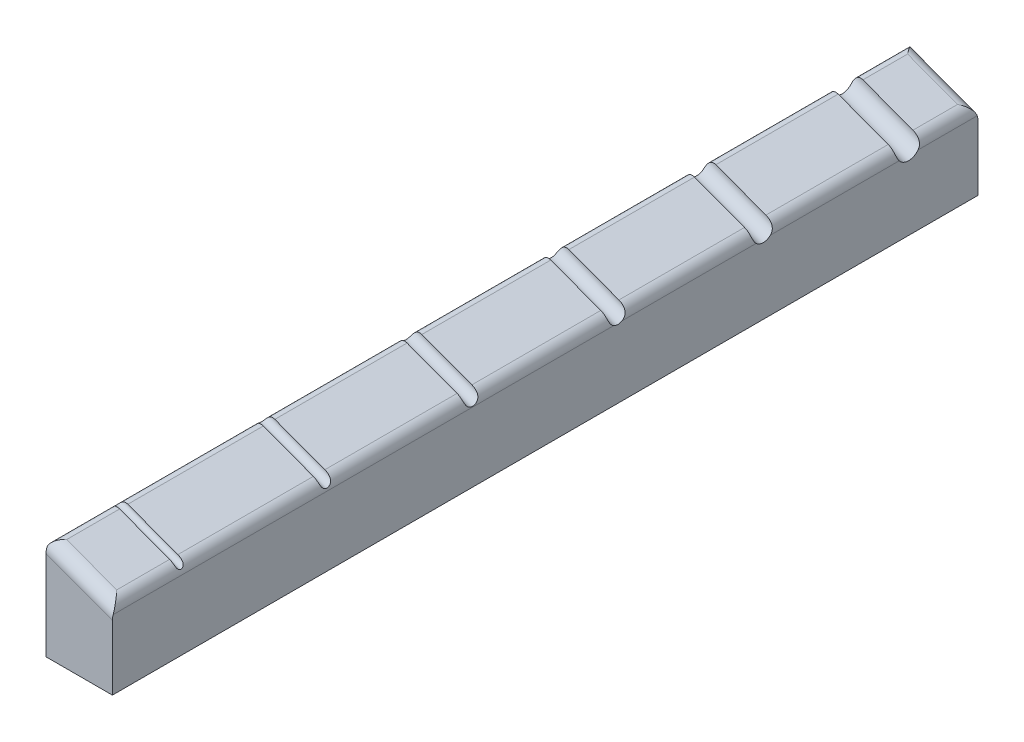
SolidWorks part; units mm, degrees
ref_plane "Front Plane" through (0, 0, 0) normal (0, 0, 1) x (1, 0, 0)
ref_plane "Top Plane" through (0, 0, 0) normal (0, 1, 0) x (1, 0, 0)
ref_plane "Right Plane" through (0, 0, 0) normal (1, 0, 0) x (0, 0, -1)
sketch "Sketch1" plane through (0, 0, 0) normal (0, 1, 0) x (1, 0, 0)
  line L1 (0, 0) -> (3.22, 0)
  line L2 (0, 0) -> (0, -41.98)
  line L3 (0, -41.98) -> (3.22, -41.98)
  line L4 (3.22, 0) -> (3.22, -41.98)
  dimension "D1" = 41.98
  dimension "D2" = 3.22
extrude "Boss-Extrude1" add sketch "Sketch1" along normal blind 4.98
sketch "Sketch2" plane through (0, 0, 41.98) normal (0, 0, 1) x (1, 0, 0)
  line L0 (0, 4.98) -> (3.22, 4.98)
  line L1 (3.22, 4.98) -> (3.22, 3.78)
  line L2 (3.22, 4.98) -> (3.22, 0) construction
  line L3 (3.22, 3.78) -> (0, 4.98)
extrude "Cut-Extrude1" cut sketch "Sketch2" against normal up to surface (41.98 mm away) up to face at (1.61, 2.49, 0)
sketch "Sketch3" plane through (1.6296, 4.3727, 0) normal (0.3492, 0.937, 0) x (0.937, -0.3492, 0)
  line L0 (-1.7391, 0) -> (-1.7391, -41.98) construction
  line L1 (-1.7391, -3.365) -> (-1.7391, -38.615) construction
  line L2 (-1.7391, -3.365) -> (3.0173, -3.365) construction
  line L3 (3.0173, -41.98) -> (3.0173, 0) construction
  line L28 (-1.7391, -10.415) -> (3.0173, -10.415) construction
  line L29 (-1.7391, -17.465) -> (3.0173, -17.465) construction
  line L30 (-1.7391, -24.515) -> (3.0173, -24.515) construction
  line L31 (-1.7391, -31.565) -> (3.0173, -31.565) construction
  line L32 (-1.7391, -38.615) -> (3.0173, -38.615) construction
  dimension "D1" = 6
ref_axis "Axis1" through (0, 4.98, 0) along (0, 0, 1)
ref_plane "Plane1" through (-1.6296, 0.6073, 0) normal (-0.937, 0.3492, 0) x (0, 0, 1)
fillet "Fillet1" radius 0.6 3 edges at (3.22, 3.78, 20.99) (1.61, 4.38, 0) (1.61, 4.38, 41.98)
fillet "Fillet2" radius 0.3 1 edges at (0, 4.98, 20.99) tangent propagation no
sketch "Sketch4" plane through (-1.6296, 0.6073, 0) normal (-0.937, 0.3492, 0) x (0, 0, 1)
  circle A0 centre (3.365, 4.6665) radius 0.6
  circle A1 centre (38.615, 4.6665) radius 0.2
  circle A2 centre (31.565, 4.6665) radius 0.28
  circle A3 centre (24.515, 4.6665) radius 0.36
  circle A4 centre (17.465, 4.6665) radius 0.44
  circle A5 centre (10.415, 4.6665) radius 0.52
extrude "Cut-Extrude2" cut sketch "Sketch4" against normal blind 4.98
